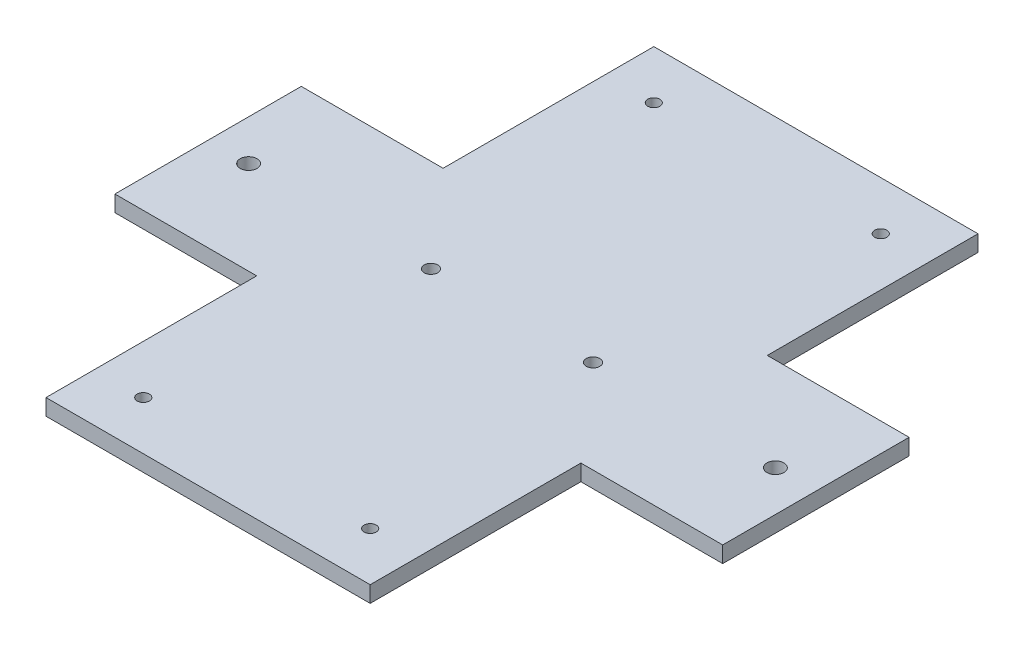
SolidWorks part; units mm, degrees
ref_plane "Front Plane" through (0, 0, 0) normal (0, 0, 1) x (1, 0, 0)
ref_plane "Top Plane" through (0, 0, 0) normal (0, 1, 0) x (1, 0, 0)
ref_plane "Right Plane" through (0, 0, 0) normal (1, 0, 0) x (0, 0, -1)
sketch "Sketch1" plane through (0, 0, 0) normal (0, 1, 0) x (1, 0, 0)
  line L0 (-75, 0) -> (75, 0) construction
  line L1 (-75, -23) -> (-40, -23)
  line L2 (-75, -23) -> (-75, 23)
  line L3 (-75, 23) -> (-40, 23)
  line L4 (75, -23) -> (75, 23)
  line L5 (-75, -23) -> (75, 23) construction
  line L6 (-75, 23) -> (75, -23) construction
  line L7 (0, 23) -> (0, -23) construction
  line L8 (-40, 23) -> (-40, 75)
  line L9 (-40, -75) -> (40, -75)
  line L10 (-40, -75) -> (-40, -23)
  line L11 (-40, 75) -> (40, 75)
  line L12 (40, -75) -> (40, -23)
  line L13 (-40, -75) -> (40, 75) construction
  line L14 (-40, 75) -> (40, -75) construction
  line L15 (40, -23) -> (75, -23)
  line L16 (40, 23) -> (75, 23)
  line L17 (40, 23) -> (40, 75)
  line L18 (-28, 63) -> (-28, -63) construction
  line L19 (-28, -63) -> (28, -63) construction
  line L20 (28, -63) -> (28, 63) construction
  line L21 (28, 63) -> (-28, 63) construction
  circle A0 centre (20, 0) radius 1.6782
  circle A1 centre (65, 0) radius 2.0828
  circle A2 centre (-65, 0) radius 2.0828
  circle A3 centre (-20, 0) radius 1.6782
  circle A4 centre (-28, 63) radius 1.5
  circle A5 centre (28, 63) radius 1.5
  circle A6 centre (28, -63) radius 1.5
  circle A7 centre (-28, -63) radius 1.5
  point P0 (0, 0)
  point P20 (0, 0)
  dimension "D7" = 3
  dimension "D8" = 3
  dimension "D9" = 3
  dimension "D10" = 3
  dimension "D1" = 150
  dimension "D2" = 46
  dimension "D3" = 20
  dimension "D4" = 45
  dimension "D5" = 80
  dimension "D6" = 150
  dimension "D11" = 12
  dimension "D12" = 12
  dimension "D13" = 12
  dimension "D14" = 12
extrude "Boss-Extrude1" add sketch "Sketch1" along normal blind 4
